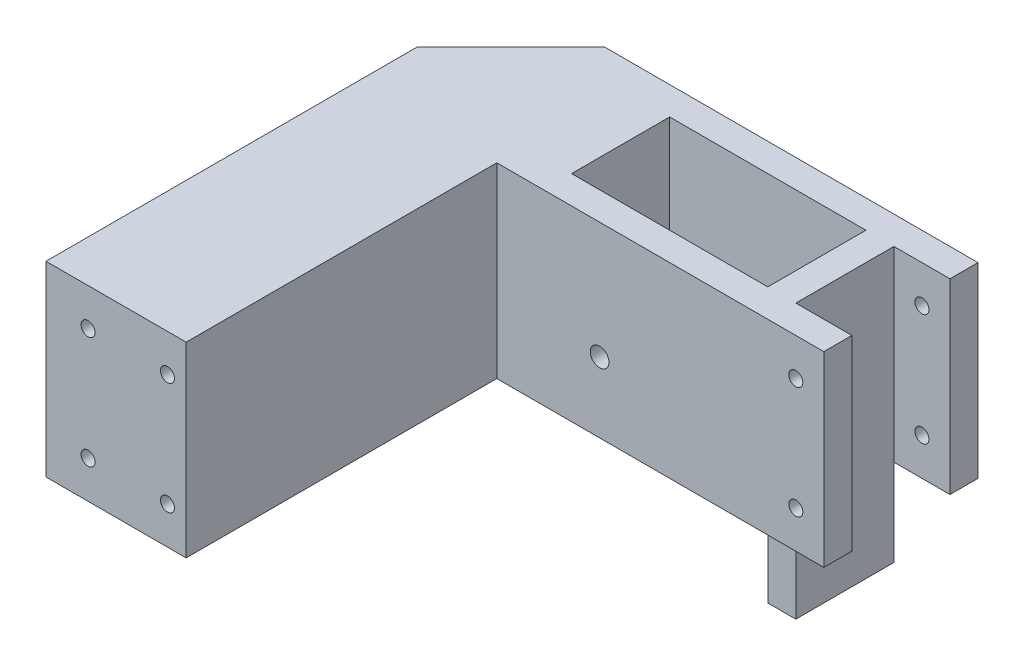
SolidWorks part; units mm, degrees
ref_plane "前视基准面" through (0, 0, 0) normal (0, 0, 1) x (1, 0, 0)
ref_plane "上视基准面" through (0, 0, 0) normal (0, 1, 0) x (1, 0, 0)
ref_plane "右视基准面" through (0, 0, 0) normal (1, 0, 0) x (0, 0, -1)
other "Configuration Table"
sketch "草图1" plane through (0, 0, 0) normal (0, 1, 0) x (1, 0, 0)
  line L1 (0, 0) -> (80, 0)
  line L3 (0, 33) -> (80, 33)
  line L9 (0, 33) -> (0, 0)
  line L10 (80, 33) -> (80, 27)
  line L11 (80, 27) -> (20, 27)
  line L12 (20, 27) -> (20, 6)
  line L13 (20, 6) -> (80, 6)
  line L14 (80, 6) -> (80, 0)
  dimension "D1" = 21
  dimension "D2" = 60
  dimension "D3" = 6
  dimension "D4" = 6
  dimension "D5" = 80
extrude "凸台-拉伸1" add sketch "草图1" along normal blind 40
sketch "草图7" plane through (0, 40, 0) normal (0, 1, 0) x (1, 0, 0)
  line L0 (0, 33) -> (0, 0) construction
  line L1 (20, 5.4804) -> (0, 5.4804)
  line L2 (20, 5.4804) -> (20, 0)
  line L3 (20, 0) -> (0, 0)
  line L4 (0, 5.4804) -> (0, 0)
  line L6 (0, 0) -> (80, 0) construction
  dimension "D1" = 5.4804
  dimension "D2" = 20
sketch "草图8" plane through (0, 0, -33) normal (0, 0, -1) x (-1, 0, 0)
  line L0 (-80, 40) -> (-80, 0) construction
  line L1 (-74, 32) -> (-6, 32) construction
  line L2 (-74, 32) -> (-74, 8) construction
  line L3 (-74, 8) -> (-6, 8) construction
  line L4 (-6, 32) -> (-6, 8) construction
  line L5 (-80, 40) -> (0, 40) construction
  circle A0 centre (-74, 8) radius 1.5
  circle A1 centre (-74, 32) radius 1.5
  circle A2 centre (-6, 32) radius 1.5
  circle A3 centre (-6, 8) radius 1.5
  dimension "D4" = 3
  dimension "D1" = 68
  dimension "D2" = 24
  dimension "D3" = 6
  dimension "D5" = 8
extrude "切除-拉伸2" cut sketch "草图8" against normal through all
sketch "草图12" plane through (0, 0, 0) normal (0, 0, 1) x (1, 0, 0)
  line L0 (0, 0) -> (80, 0) construction
  line L1 (10, 0) -> (-20, 0)
  line L2 (10, 0) -> (10, 40)
  line L3 (10, 40) -> (-20, 40)
  line L4 (-20, 0) -> (-20, 40)
  line L5 (0, 40) -> (80, 40) construction
  line L6 (0, 40) -> (0, 0) construction
  line L7 (-11, 32) -> (6, 32) construction
  line L9 (6, 8) -> (-11, 8) construction
  circle A0 centre (-11, 32) radius 1.5
  circle A1 centre (-11, 8) radius 1.5
  circle A2 centre (6, 8) radius 1.5 construction
  circle A3 centre (6, 32) radius 1.5 construction
  circle A4 centre (6, 8) radius 1.5
  circle A5 centre (6, 32) radius 1.5
  dimension "D3" = 3
  dimension "D4" = 3
  dimension "D1" = 30
  dimension "D2" = 20
  dimension "D5" = 17
extrude "凸台-拉伸7" add sketch "草图12" along normal blind 66.5 and the other way up to surface other way up to face at (4.5, 8, -33)
sketch "草图14" plane through (0, 40, 0) normal (0, 1, 0) x (1, 0, 0)
  line L0 (-20, 33) -> (0, 33)
  line L1 (80, 33) -> (-20, 33) construction
  line L2 (0, 33) -> (-20, 13)
  line L3 (-20, 33) -> (-20, -66.5) construction
  line L4 (-20, 13) -> (-20, 33)
  dimension "D1" = 20
  dimension "D2" = 20
extrude "切除-拉伸3" cut sketch "草图14" against normal through all
sketch "草图15" plane through (0, 0, 66.5) normal (0, 0, 1) x (1, 0, 0)
  circle A0 centre (-11, 32) radius 3.5
  circle A1 centre (-11, 8) radius 3.5
  dimension "D1" = 7
  dimension "D2" = 7
extrude "切除-拉伸4" cut sketch "草图15" against normal through all from offset 50 offset against normal yes
sketch "草图16" plane through (0, 40, 0) normal (0, 1, 0) x (1, 0, 0)
  line L0 (20, 27) -> (80, 27) construction
  line L1 (62, 27) -> (68, 27)
  line L2 (62, 27) -> (62, 6)
  line L3 (62, 6) -> (68, 6)
  line L4 (68, 27) -> (68, 6)
  line L5 (80, 6) -> (20, 6) construction
  line L6 (20, 6) -> (20, 27) construction
  dimension "D1" = 6
  dimension "D2" = 42
extrude "凸台-拉伸9" add sketch "草图16" along normal up to surface and the other way blind 18.6 from surface up to face at (30.9091, 40, -1.0909) starting at face at (30.9091, 0, -1.0909)
sketch "草图17" plane through (0, 0, 0) normal (0, 0, 1) x (1, 0, 0)
  line L0 (10, 40) -> (10, 0) construction
  line L1 (10, 40) -> (80, 40) construction
  circle A0 centre (32, 15) radius 2
  dimension "D3" = 4
  dimension "D1" = 22
  dimension "D2" = 25
extrude "切除-拉伸5" cut sketch "草图17" against normal through all
